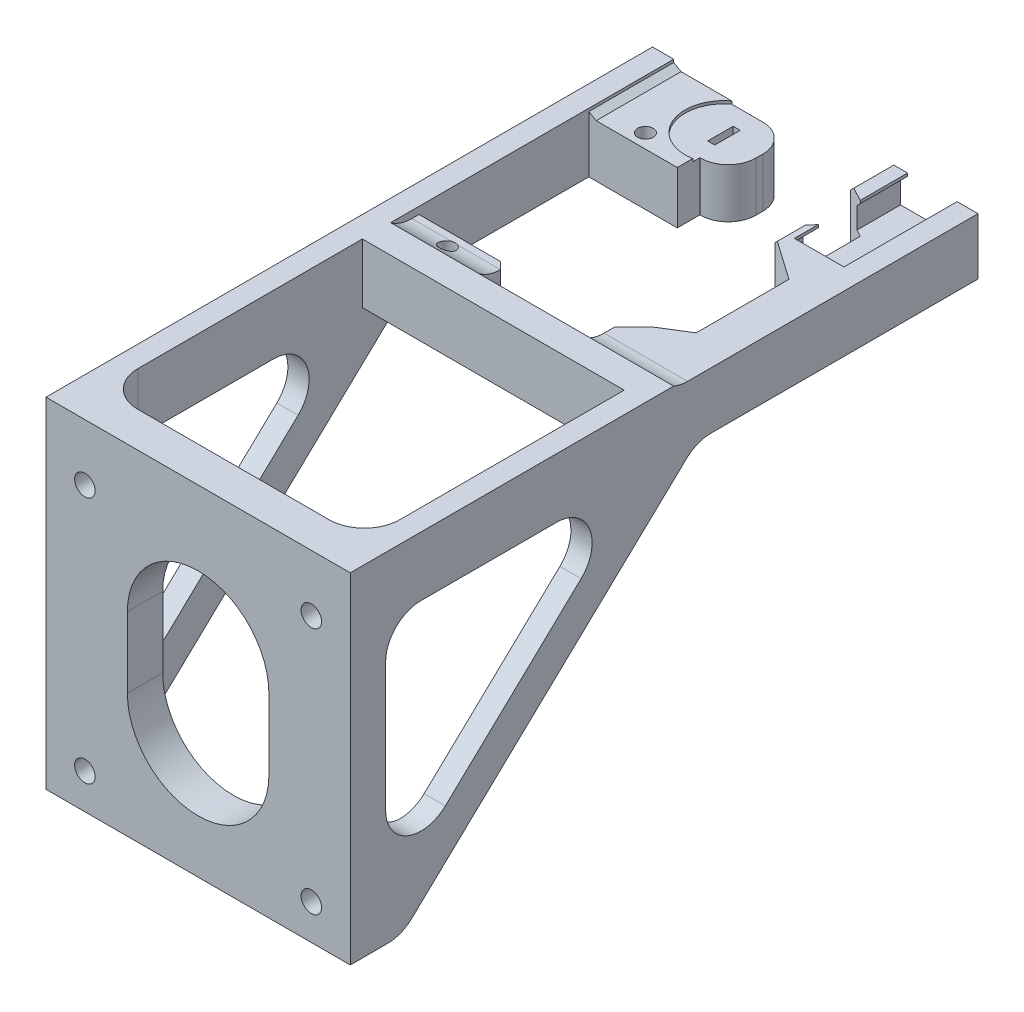
SolidWorks part; units mm, degrees
ref_plane "Front Plane" through (0, 0, 0) normal (0, 0, 1) x (1, 0, 0)
ref_plane "Top Plane" through (0, 0, 0) normal (0, 1, 0) x (1, 0, 0)
ref_plane "Right Plane" through (0, 0, 0) normal (1, 0, 0) x (0, 0, -1)
sketch "Sketch1" plane through (0, 0, 0) normal (0, 1, 0) x (1, 0, 0)
  line L0 (0, 0) -> (0, 59.6401) construction
  line L1 (-18.5, -19.2885) -> (-21.5, -19.2885)
  line L2 (18.5, 17.7115) -> (21.5, 17.7115)
  line L3 (18.5, 17.7115) -> (18.5, 65.7115)
  line L4 (18.5, 65.7115) -> (21.5, 65.7115)
  line L5 (21.5, 17.7115) -> (21.5, 65.7115)
  line L6 (18.5, 17.7115) -> (21.5, 17.7115)
  line L7 (18.5, 17.7115) -> (18.5, -19.2885)
  line L8 (18.5, -19.2885) -> (21.5, -19.2885)
  line L9 (21.5, 17.7115) -> (21.5, -19.2885)
  line L10 (-21.5, 17.7115) -> (-21.5, -19.2885)
  line L11 (-18.5, 17.7115) -> (-21.5, 17.7115)
  line L12 (-18.5, 17.7115) -> (-18.5, -19.2885)
  line L13 (-18.5, 65.7115) -> (-21.5, 65.7115)
  line L14 (-21.5, 17.7115) -> (-21.5, 65.7115)
  line L15 (-18.5, 17.7115) -> (-21.5, 17.7115)
  line L16 (-18.5, 17.7115) -> (-18.5, 65.7115)
  dimension "18" = 18.5
  dimension "D2" = 3
  dimension "D3" = 37
  dimension "D4" = 48
extrude "Boss-Extrude1" add sketch "Sketch1" against normal blind 8 contours L12 L11 L10 L1 | L11 L16 L13 L14 | L9 L2 L7 L8 | L2 L5 L4 L3 region at (-20, 0, 0.7885) region at (-20, 0, -41.7115) region at (20, 0, -41.7115) region at (20, 0, 0.7885)
sketch "Sketch2" plane through (21.5, 0, 0) normal (1, 0, 0) x (0, 0, -1)
  line L0 (-19.2885, -4) -> (65.7115, -4) construction
  line L1 (-19.2885, -8) -> (-19.2885, 0) construction
  line L2 (65.7115, -8) -> (65.7115, 0) construction
  line L3 (65.7115, -8) -> (-19.2885, -8) construction
  line L4 (17.7115, 0) -> (17.7115, -8) construction
  line L5 (65.7115, 0) -> (-19.2885, 0) construction
  circle A0 centre (11.7115, -4) radius 1.5
  circle A2 centre (-8.2885, -4) radius 1.5
  circle A3 centre (1.7115, -4) radius 1.5 [skipped]
  dimension "D2" = 3
  dimension "D1" = 4
  dimension "D3" = 37
  dimension "D4" = 6
  dimension "D5" = 3
extrude "Cut-Extrude1" [suppressed] cut sketch "Sketch2" against normal through all both and the other way through all
chamfer "Chamfer1" [suppressed] distance 1 angle 48
chamfer "Chamfer2" [suppressed] distance 1 angle 48
sketch "Sketch4" plane through (0, -8, 0) normal (0, -1, 0) x (1, 0, 0)
  line L0 (-21.5, -65.7115) -> (-21.5, 19.2885) construction
  line L1 (-2, -65.7115) -> (-21.5, -65.7115)
  line L2 (-2, -65.7115) -> (-2, -56.9115)
  line L3 (-2, -56.9115) -> (-21.5, -56.9115)
  line L4 (-21.5, -65.7115) -> (-21.5, -56.9115)
  line L10 (-18.5, -65.7115) -> (-18.5, 19.2885) construction
  line L13 (-18.5, -65.7115) -> (-21.5, -65.7115) construction
  dimension "D1" = 8.8
  dimension "D2" = 16.5
extrude "Boss-Extrude3" add sketch "Sketch4" against normal blind 6.6
sketch "Sketch3" plane through (0, -8, 0) normal (0, -1, 0) x (1, 0, 0)
  line L0 (-21.5, -65.7115) -> (-21.5, 19.2885) construction
  line L1 (-21.5, -57.7115) -> (-6, -57.7115)
  line L2 (-21.5, -57.7115) -> (-21.5, -53.7115)
  line L3 (-21.5, -53.7115) -> (-6, -53.7115)
  line L4 (-6, -57.7115) -> (-6, -53.7115)
  line L6 (0, 0) -> (0, -31.4212) construction
  line L13 (-2, -65.7115) -> (-21.5, -65.7115) construction
  line L14 (-21.5, -41.7115) -> (-3.8096, -41.7115) construction
  line L15 (-21.5, -29.7115) -> (-6, -29.7115)
  line L16 (-6, -25.7115) -> (-6, -29.7115)
  line L17 (-21.5, -25.7115) -> (-6, -25.7115)
  line L18 (-21.5, -25.7115) -> (-21.5, -29.7115)
  line L19 (-18.5, -56.9115) -> (-18.5, 19.2885) construction
  circle A0 centre (-12.5, -55.7115) radius 1.04
  circle A2 centre (-12.5, -27.7115) radius 1.04
  dimension "D4" = 2
  dimension "D5" = 2.08
  dimension "D1" = 14
  dimension "D2" = 10
  dimension "D3" = 4
  dimension "D6" = 6
  dimension "D7" = 15.5
extrude "Servo Holder" add sketch "Sketch3" along normal blind 0.4 and the other way offset from surface 1 other way up to plane "Top Plane"
sketch "Sketch5" plane through (0, 0, 0) normal (0, 1, 0) x (1, 0, 0)
  line L0 (-2, 61.3115) -> (-21.5, 61.3115) construction
  line L1 (-2, 65.7115) -> (-2, 56.9115) construction
  line L2 (-21.5, 65.7115) -> (-21.5, -19.2885) construction
  line L4 (-6.5, 63.1115) -> (-7.5, 63.1115)
  line L5 (-6.5, 63.1115) -> (-6.5, 59.5115)
  line L6 (-6.5, 59.5115) -> (-7.5, 59.5115)
  line L7 (-7.5, 63.1115) -> (-7.5, 59.5115)
  line L8 (-6.5, 63.1115) -> (-7.5, 59.5115) construction
  line L9 (-6.5, 59.5115) -> (-7.5, 63.1115) construction
  circle A0 centre (-12.5, 55.7115) radius 1.04 construction
  point P6 (-7, 61.3115)
  dimension "D3" = 5.5
  dimension "D1" = 1
  dimension "D2" = 3.6
extrude "Cut-Extrude2" cut sketch "Sketch5" against normal through all
sketch "Sketch6" plane through (0, -1.4, 0) normal (0, 1, 0) x (1, 0, 0)
  line L0 (-6.5, 61.3115) -> (-7.5, 61.3115) construction
  line L1 (-6.5, 59.5115) -> (-6.5, 63.1115) construction
  line L2 (-7.5, 63.1115) -> (-7.5, 59.5115) construction
  circle A0 centre (-7, 61.3115) radius 5.25
  dimension "D1" = 10.5
extrude "Brass" [suppressed] add sketch "Sketch6" along normal blind 2.6
fillet "Fillet1" [suppressed] radius 2.6
sketch "Sketch11" plane through (0, -8, 0) normal (0, -1, 0) x (1, 0, 0)
  line L0 (21.5, -65.7115) -> (21.5, 19.2885) construction
  line L1 (-21.5, -25.7115) -> (21.5, -25.7115)
  line L2 (-21.5, -25.7115) -> (-21.5, -21.7115)
  line L3 (-21.5, -21.7115) -> (21.5, -21.7115)
  line L4 (21.5, -25.7115) -> (21.5, -21.7115)
  dimension "D1" = 4
extrude "Boss-Extrude9" add sketch "Sketch11" against normal blind 8 and the other way up to surface (0.4 mm away) other way up to face at (-13.75, -8.4, -55.7115)
sketch "Sketch14" plane through (0, -8, 0) normal (0, -1, 0) x (1, 0, 0)
  line L1 (18.5, -25.7115) -> (30.7236, -25.7115)
  line L2 (18.5, -25.7115) -> (18.5, -70.6911)
  line L3 (18.5, -70.6911) -> (30.7236, -70.6911)
  line L4 (30.7236, -25.7115) -> (30.7236, -70.6911)
extrude "Cut-Extrude5" cut sketch "Sketch14" against normal blind 10
fillet "Fillet2" radius 3.9 2 edges at (-2, -4.7, -65.7115) (-2, -4.7, -56.9115)
sketch "Sketch13" plane through (0, -8.4, 0) normal (0, -1, 0) x (-1, 0, 0)
  circle A0 centre (12.5, 55.7115) radius 1.1
  circle A1 centre (12.5, 27.7115) radius 1.1
  dimension "D1" = 2.2
extrude "Cut-Extrude4" cut sketch "Sketch13" against normal through all both and the other way through all
sketch "Sketch17" plane through (0, 0, -25.7115) normal (0, 0, -1) x (-1, 0, 0)
  line L0 (-21.5, -8.4) -> (6, -8.4) construction
  line L1 (-8.6, -8.4) -> (-21.5, -8.4)
  line L2 (-8.6, -8.4) -> (-8.6, -0.4)
  line L3 (-8.6, -0.4) -> (-21.5, -0.4)
  line L4 (-21.5, -8.4) -> (-21.5, -0.4)
  line L5 (-21.5, -8.4) -> (-21.5, 0) construction
  dimension "D1" = 12.9
  dimension "D2" = 8
extrude "Boss-Extrude11" add sketch "Sketch17" along normal blind 27
sketch "Sketch16" plane through (0, 0, -52.7115) normal (0, 0, -1) x (-1, 0, 0)
  line L0 (-18.55, -2) -> (-18.55, -0.4)
  line L1 (-10.55, -4.8) -> (-19.75, -4.8)
  line L2 (-10.55, -4.8) -> (-10.55, -2)
  line L3 (-10.55, -2) -> (-19.75, -2)
  line L4 (-19.75, -4.8) -> (-19.75, -2)
  line L5 (-18.55, -0.4) -> (-21.5, -0.4)
  line L6 (-21.5, -0.4) -> (-21.5, -8.4)
  line L7 (-21.5, -8.4) -> (-8.6, -8.4)
  line L8 (-15.05, -4.3136) -> (-15.05, -1.3136) construction
  line L9 (-8.6, -8.4) -> (6, -8.4) construction
  line L10 (-8.6, -0.4) -> (-8.6, -8.4)
  line L11 (-11.55, -2) -> (-11.55, -0.4)
  line L12 (-11.55, -0.4) -> (-8.6, -0.4)
  line L13 (-21.5, -0.4) -> (-21.5, 0) construction
  line M30 (-8.6, -8.4) -> (-8.6, -0.4)
  line M31 (-8.6, -0.4) -> (-21.5, -0.4)
  line M32 (-21.5, -0.4) -> (-21.5, -8.4)
  line M33 (-21.5, -8.4) -> (-8.6, -8.4)
  dimension "D1" = 2.8
  dimension "D2" = 9.2
  dimension "D3" = 1.6
  dimension "D4" = 1.75
  dimension "D5" = 3.6
  dimension "D6" = 3.5
  dimension "D7" = 1.95
extrude "Boss-Extrude12" add sketch "Sketch16" along normal offset from surface (16 mm away) 3 contours L11 L3 L2 L1 L4 L0 M31 M32 M33 M30 region at (15.0111, -5.33, -52.7115) up to face at (-15.3, -3.1333, -65.7115) offset beyond the face yes
sketch "Sketch18" plane through (0, -8, 0) normal (0, -1, 0) x (1, 0, 0)
  line L0 (18.5, 19.2885) -> (21.5, 19.2885) construction
  line L1 (-21.5, -65.7115) -> (-5.9, -65.7115)
  line L2 (-21.5, -65.7115) -> (-21.5, -52.3785)
  line L5 (-21.5, -57.7115) -> (-18.5, -57.7115)
  line L6 (-21.5, -57.7115) -> (-21.5, 19.2885)
  line L7 (-21.5, 19.2885) -> (-18.5, 19.2885)
  line L8 (-18.5, -57.7115) -> (-18.5, 19.2885)
  line L9 (21.5, 19.2885) -> (18.5, 19.2885)
  line L10 (21.5, 19.2885) -> (21.5, -21.7115)
  line L11 (21.5, -21.7115) -> (18.5, -21.7115)
  line L12 (18.5, 19.2885) -> (18.5, -21.7115)
  line L13 (-18.5, 19.2885) -> (-21.5, 19.2885) construction
  line L14 (21.5, -21.7115) -> (21.5, 19.2885) construction
  line L15 (-18.5, -53.7115) -> (-18.5, -29.7115) construction
  line L16 (-2, -61.8115) -> (-2, -60.8115) construction
  arc A0 (-5.9, -56.9115) -> (-2, -60.8115) centre (-5.9, -60.8115) cw
  arc A1 (-5.9, -65.7115) -> (-2, -61.8115) centre (-5.9, -61.8115) ccw
  arc A5 (-2, -60.8115) -> (-5.9, -56.9115) centre (-5.9, -60.8115) ccw construction
  arc A6 (-5.9, -65.7115) -> (-2, -61.8115) centre (-5.9, -61.8115) ccw construction
  line M7 (-6.5, -63.1115) -> (-7.5, -63.1115)
  line M8 (-7.5, -63.1115) -> (-7.5, -59.5115)
  line M9 (-7.5, -59.5115) -> (-6.5, -59.5115)
  line M10 (-6.5, -59.5115) -> (-6.5, -63.1115)
  line M11 (-21.5, -65.7115) -> (-5.9, -65.7115)
  line M13 (-2, -61.8115) -> (-2, -60.8115)
  line M15 (-5.9, -56.9115) -> (-6, -56.9115)
  line M16 (-6, -56.9115) -> (-6, -57.7115)
  line M17 (-6, -57.7115) -> (-21.5, -57.7115)
  line M18 (-21.5, -57.7115) -> (-21.5, -65.7115)
extrude "Boss-Extrude13" add sketch "Sketch18" along normal up to surface (0.4 mm away) contours A1 A0 M11 M13 M15 M16 M17 M18 M10 M7 M8 M9 | L8 L7 L6 | L9 L12 L11 L10 | L6 L5 L8 L7 region at (-12.0872, -8, -61.6443) region at (-20, -8, -19.2115) region at (20, -8, -1.2115) up to face at (-12.5, -8.4, -26.6115)
chamfer "Chamfer14" distance 1.2 angle 45 2 edges at (18.55, -2, -60.7115) (11.55, -2, -60.7115)
sketch "Sketch20" plane through (0, -0.4, 0) normal (0, 1, 0) x (1, 0, 0)
  line L0 (11.55, 62.0219) -> (2.5155, 66.7653)
  line L1 (11.55, 68.7115) -> (11.55, 52.7115) construction
  line L2 (2.5155, 66.7653) -> (1.9978, 58.6591)
  line L3 (1.9978, 58.6591) -> (1.9978, 45.1224)
  line L4 (1.9978, 45.1224) -> (11.55, 56.0872)
  line L5 (11.55, 56.0872) -> (11.55, 62.0219)
  line L6 (8.6, 25.7115) -> (21.5, 25.7115) construction
  line L7 (9.7, 25.7115) -> (1.9978, 25.7115)
  line L8 (9.7, 25.7115) -> (9.7, 53.9636)
  line L9 (9.7, 53.9636) -> (1.9978, 53.9636)
  line L10 (1.9978, 25.7115) -> (1.9978, 53.9636)
  line L11 (21.5, 68.7115) -> (21.5, 25.7115) construction
  line L12 (16.1748, 47.3223) -> (4.9747, 55.1624)
  line L13 (4.9747, 55.1624) -> (4.9747, 27.2638)
  line L14 (4.9747, 27.2638) -> (16.1748, 34.2118)
  line L15 (16.1748, 34.2118) -> (16.1748, 47.3223)
  line M6 (8.6, 25.7115) -> (21.5, 25.7115)
  line M11 (11.55, 52.7115) -> (11.55, 68.7115)
  line M13 (8.6, 68.7115) -> (8.6, 25.7115)
  dimension "D1" = 11.8
extrude "Cut-Extrude6" cut sketch "Sketch20" against normal through all both and the other way through all contours L13 L12 L9 L0 L2 L3 M13 | L12 L9 M13 | L12 L4 L9 M13 | L12 L8 L4 | L14 L8 L12 L4 M13 | L14 L15 L12 L8 | L13 L14 L4 M13 | L9 L13 L4 L12 M13 | L12 L13 L9 | L9 L4 L0 M11 M13 | L4 L12 M13 | L14 L8 M13 M6 region at (9.9584, -0.4, -58.6946) region at (5.2143, -0.4, -59.6186) region at (7.9616, -0.4, -53.5183) region at (8.9667, -0.4, -53.5427) region at (9.3205, -0.4, -52.8242) region at (6.2284, -0.4, -51.906) region at (5.5455, -0.4, -54.3632) region at (12.6721, -0.4, -40.9066) region at (9.1441, -0.4, -41.0471) region at (6.8133, -0.4, -39.527) region at (9.1651, -0.4, -27.7874)
chamfer "Chamfer19" [suppressed] distance 0.7 angle 33
ref_plane "Plane1" through (0, 20.6, 0) normal (0, 1, 0) x (1, 0, 0)
sketch "Sketch29" plane through (0, -1.4, 0) normal (0, 1, 0) x (1, 0, 0)
  line L0 (-18.5, 57.7115) -> (-6, 57.7115) construction
  line L1 (-18.5, 65.7115) -> (-9.6141, 65.7115)
  line L2 (-18.5, 65.7115) -> (-18.5, 57.7115)
  line L3 (-18.5, 57.7115) -> (-9.6141, 57.7115)
  line L4 (-9.6141, 65.7115) -> (-9.6141, 57.7115)
extrude "Boss-Extrude20" add sketch "Sketch29" along normal up to surface (0.4 mm away) up to face at (-12.5, -1, -54.6115)
sketch "Sketch25" [suppressed] plane through (0, 0, -17.7115) normal (0, 0, -1) x (-1, 0, 0)
  line L0 (21.5, 20.6) -> (21.5, 0) construction
  line L1 (-21.5, -0.4) -> (21.5, -0.4)
  line L2 (-21.5, -0.4) -> (-21.5, 0.5976)
  line L3 (-21.5, 0.5976) -> (21.5, 0.5976)
  line L4 (21.5, -0.4) -> (21.5, 0.5976)
  line L6 (18.5, -1) -> (0, -1)
  line L7 (18.5, -1) -> (18.5, -1.6016)
  line L8 (18.5, -1.6016) -> (0, -1.6016)
  line L9 (0, -1) -> (0, -1.6016)
extrude "Cut-Extrude7" [suppressed] cut sketch "Sketch25" along normal through all
chamfer "Chamfer22" [suppressed] distance 2 angle 45
chamfer "Chamfer23" distance 1 angle 45 1 edges at (9.7, -0.4, -52.9091)
chamfer "Chamfer24" distance 1 angle 45 3 edges at (8.6, -0.4, -66.1411) (-6, -4.7, -29.7115) (9.7, -4.4, -30.1952) first distance on face at (8.6, -4.4, -66.1411) first distance on face at (-6, -4.7, -27.7115) first distance on face at (9.7, -4.4, -27.9534)
sketch "Sketch26" plane through (0, -1.4, 0) normal (0, 1, 0) x (1, 0, 0)
  line L0 (-7.5, 63.1115) -> (-6.5, 63.1115) construction
  line L1 (-7.5, 59.5115) -> (-7.5, 63.1115) construction
  circle A0 centre (-7, 61.3115) radius 5.5
  dimension "D1" = 11
  dimension "D2" = 1.8
  dimension "D3" = 0.5
extrude "Cut-Extrude8" cut sketch "Sketch26" along normal blind 10
chamfer "Chamfer25" distance 0.6 angle 60 1 edges at (-18.5, -1, -59.7115) first distance on face at (-18.5, -2.6, -43.7115)
ref_plane "Plane2" through (0, 0, 20) normal (0, 0, 1) x (1, 0, 0)
sketch "Sketch30" plane through (0, 0, 20) normal (0, 0, 1) x (1, 0, 0)
  line L0 (0, 0) -> (0, -66.7325) construction
  line L1 (-21.5, -25.5) -> (21.5, -25.5) construction
  line L2 (-21.5, 0) -> (21.5, 0)
  line L3 (-21.5, 0) -> (-21.5, -48)
  line L4 (-21.5, -48) -> (21.5, -48)
  line L5 (21.5, 0) -> (21.5, -48)
  line L6 (0, -20.5) -> (0, -30.5) construction
  line L7 (10, -20.5) -> (10, -30.5)
  line L8 (-10, -20.5) -> (-10, -30.5)
  circle A0 centre (-16, -8) radius 1.45
  circle A1 centre (16, -8) radius 1.45
  circle A2 centre (16, -43) radius 1.45
  circle A3 centre (-16, -43) radius 1.45
  arc A4 (10, -20.5) -> (-10, -20.5) centre (0, -20.5) ccw
  arc A5 (-10, -30.5) -> (10, -30.5) centre (0, -30.5) ccw
  point P20 (0, -25.5)
  point P25 (0, -35.3512)
  dimension "D3" = 2.9
  dimension "D6" = 8
  dimension "D1" = 16
  dimension "D2" = 17.5
  dimension "D4" = 5
  dimension "D5" = 10
  dimension "D7" = 5
extrude "Boss-Extrude21" add sketch "Sketch30" against normal blind 5
sketch "Sketch31" plane through (-21.5, 0, 0) normal (-1, 0, 0) x (0, 0, 1)
  line L0 (20, -48) -> (-21.7115, -8.4)
  line L1 (-65.7115, -8.4) -> (15, -8.4) construction
  line L2 (-21.7115, -8.4) -> (-28.9736, -8.4)
  line L3 (-28.9736, -8.4) -> (12.738, -48)
  line L4 (20, -48) -> (12.738, -48)
  line L5 (15, -48) -> (20, -48) construction
  point P2 (0, 0)
  point P5 (10, -51.5495)
  point P6 (15, -51.0573)
  point P10 (20, -51.0573)
  dimension "D1" = 0
  dimension "D2" = 5
extrude "Boss-Extrude22" add sketch "Sketch31" against normal blind 3
mirror "Mirror1" about plane through (0, 0, 0) normal (1, 0, 0) of "Boss-Extrude22"
fillet "Fillet3" radius 5 6 edges at (-20, -8.4, -21.7115) (-20, -8.4, 15) (-20, -43.2531, 15) (20, -43.2531, 15) (20, -8.4, 15) (20, -8.4, -21.7115)
fillet "Fillet4" radius 5 6 edges at (-12.25, -1, -25.7115) (15.6, -0.4, -25.7115) (-20, -8.4, -28.9736) (20, -8.4, -28.9736) (-20, -48, 12.738) (20, -48, 12.738)
fillet "Fillet5" radius 5 4 edges at (-18.5, -6.7, 15) (-18.5, -39.8059, 15) (18.5, -39.8059, 15) (18.5, -6.7, 15)
